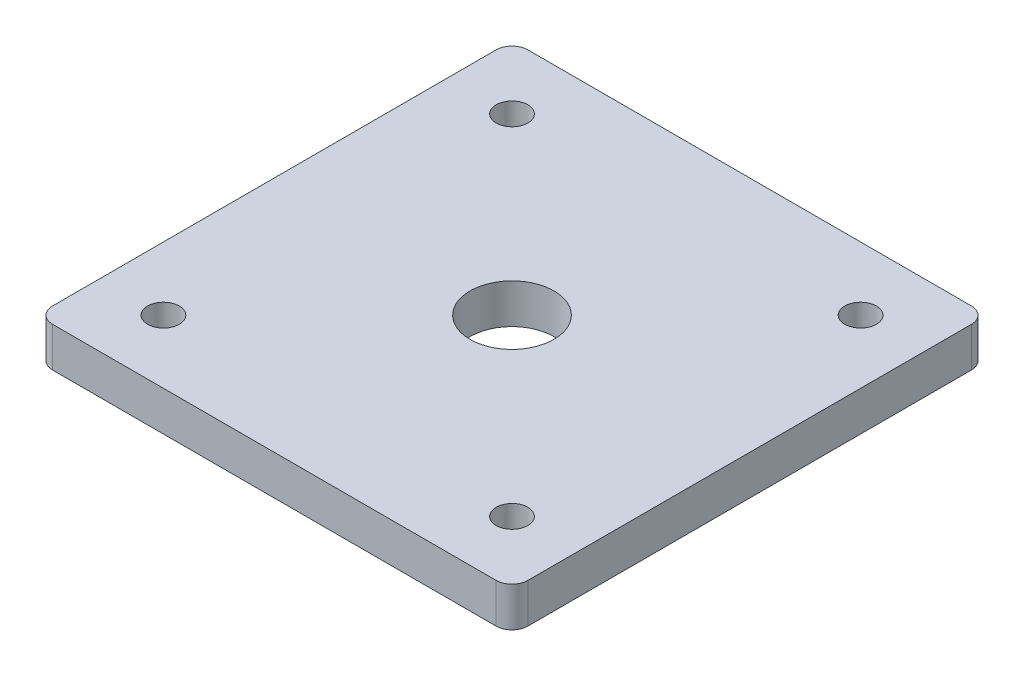
SolidWorks part; units mm, degrees
material "Acrylic (Medium-high impact)"
ref_plane "Front" through (0, 0, 0) normal (0, 0, 1) x (1, 0, 0)
ref_plane "Top" through (0, 0, 0) normal (0, 1, 0) x (1, 0, 0)
ref_plane "Right" through (0, 0, 0) normal (1, 0, 0) x (0, 0, -1)
sketch "Sketch1" plane through (0, 0, 0) normal (0, 0, 1) x (1, 0, 0)
  line L0 (-22.225, 0) -> (22.225, 0)
  dimension "D1" = 44.45
sketch "Sketch2" plane through (0, 0, 0) normal (0, 1, 0) x (1, 0, 0)
  line L0 (-13.97, 13.97) -> (13.97, 13.97) construction
  line L1 (-13.97, 13.97) -> (-13.97, -13.97) construction
  line L2 (-13.97, -13.97) -> (13.97, -13.97) construction
  line L3 (13.97, 13.97) -> (13.97, -13.97) construction
  line L4 (-13.97, 13.97) -> (13.97, -13.97) construction
  line L5 (-13.97, -13.97) -> (13.97, 13.97) construction
  line L7 (-19.05, 19.05) -> (19.05, 19.05)
  line L8 (-19.05, 19.05) -> (-19.05, -19.05)
  line L9 (-19.05, -19.05) -> (19.05, -19.05)
  line L10 (19.05, 19.05) -> (19.05, -19.05)
  line L11 (-19.05, 19.05) -> (19.05, -19.05) construction
  line L12 (-19.05, -19.05) -> (19.05, 19.05) construction
  circle A0 centre (-13.97, 13.97) radius 1.27
  circle A1 centre (-13.97, -13.97) radius 1.27
  circle A2 centre (13.97, -13.97) radius 1.27
  circle A3 centre (13.97, 13.97) radius 1.27
  circle A4 centre (0, 0) radius 3.3655
  point P0 (0, 0)
  point P12 (0, 0)
  dimension "D3" = 2.54
  dimension "D5" = 6.731
  dimension "D1" = 27.94
  dimension "D2" = 27.94
  dimension "D4" = 38.1
extrude "Boss-Extrude1" add sketch "Sketch2" along normal blind 3.175
fillet "Fillet1" radius 1.27 4 edges at (-19.05, 1.5875, -19.05) (19.05, 1.5875, -19.05) (19.05, 1.5875, 19.05) (-19.05, 1.5875, 19.05)
